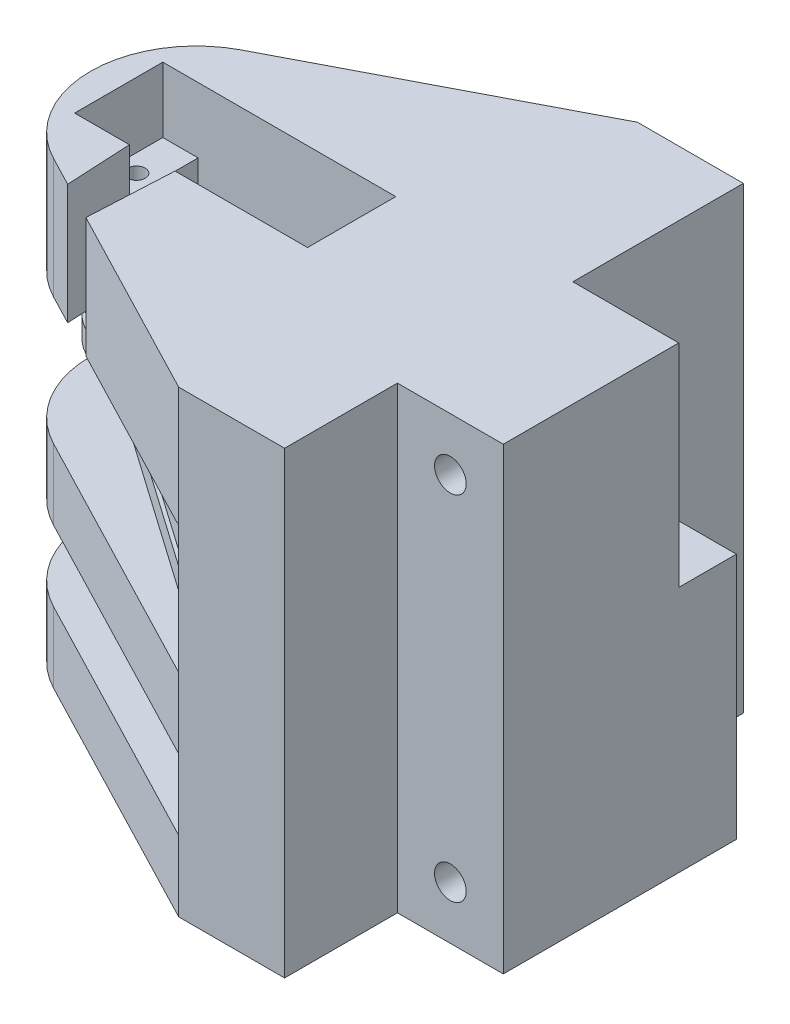
SolidWorks part; units mm, degrees
material "Copper"
ref_plane "Front Plane" through (0, 0, 0) normal (0, 0, 1) x (1, 0, 0)
ref_plane "Top Plane" through (0, 0, 0) normal (0, 1, 0) x (1, 0, 0)
ref_plane "Right Plane" through (0, 0, 0) normal (1, 0, 0) x (0, 0, -1)
sketch "Sketch1" plane through (0, 0, 0) normal (0, 0, 1) x (1, 0, 0)
  line L1 (0, 0) -> (75, 0)
  line L2 (0, 0) -> (0, 65)
  line L3 (0, 65) -> (75, 65)
  line L4 (75, 0) -> (75, 65)
  dimension "D1" = 65
  dimension "D2" = 75
extrude "Boss-Extrude1" add sketch "Sketch1" along normal blind 65
sketch "Sketch3" plane through (0, 0, 0) normal (0, -1, 0) x (1, 0, 0)
  line L0 (75, 32.5) -> (0, 32.5) construction
  line L1 (75, 65) -> (75, 0) construction
  line L2 (0, 65) -> (0, 0) construction
  line L3 (60, 49.01) -> (60, 32.5) construction
  line L4 (75, 65) -> (60, 65)
  line L5 (75, 65) -> (75, 49.01)
  line L6 (75, 49.01) -> (60, 49.01)
  line L7 (60, 65) -> (60, 49.01)
  line L8 (75, 0) -> (60, 0)
  line L9 (75, 0) -> (75, 15.99)
  line L10 (75, 15.99) -> (60, 15.99)
  line L11 (60, 0) -> (60, 15.99)
  line L12 (60, 32.5) -> (60, 15.99) construction
  dimension "D1" = 15
  dimension "D2" = 16.51
extrude "Cut-Extrude1" cut sketch "Sketch3" against normal blind 65.72
sketch "Sketch4" plane through (0, 0, 49.01) normal (0, 0, 1) x (1, 0, 0)
  line L0 (67.5, 0) -> (67.5, 65) construction
  line L1 (60, 0) -> (75, 0) construction
  line L2 (67.5, 7.5) -> (67.5, 0) construction
  line L3 (60, 65) -> (75, 65) construction
  line L4 (67.5, 65) -> (67.5, 57.5) construction
  circle A0 centre (67.5, 7.5) radius 2.2451
  circle A1 centre (67.5, 57.5) radius 2.2451
  dimension "D1" = 4.4901
  dimension "D3" = 7.5
  dimension "D4" = 4.4901
  dimension "D2" = 7.5
extrude "Cut-Extrude2" cut sketch "Sketch4" against normal blind 45.72
sketch "Sketch5" plane through (0, 0, 0) normal (-1, 0, 0) x (0, 0, 1)
  line L0 (65, 65) -> (65, 0) construction
  line L1 (0, 0) -> (65, 0)
  line L2 (0, 0) -> (0, 10)
  line L3 (0, 10) -> (65, 10)
  line L4 (65, 0) -> (65, 10)
  line L6 (0, 10) -> (65, 10)
  line L7 (0, 10) -> (0, 20)
  line L8 (0, 20) -> (65, 20)
  line L9 (65, 10) -> (65, 20)
  line L10 (0, 20) -> (65, 20)
  line L11 (0, 20) -> (0, 30)
  line L12 (0, 30) -> (65, 30)
  line L13 (65, 20) -> (65, 30)
  line L14 (0, 30) -> (65, 30)
  line L15 (0, 30) -> (0, 40)
  line L16 (0, 40) -> (65, 40)
  line L17 (65, 30) -> (65, 40)
  line L18 (0, 40) -> (65, 40)
  line L19 (0, 40) -> (0, 43)
  line L20 (0, 43) -> (65, 43)
  line L21 (65, 40) -> (65, 43)
  line L22 (0, 43) -> (65, 43)
  line L23 (0, 43) -> (0, 45)
  line L24 (0, 45) -> (65, 45)
  line L25 (65, 43) -> (65, 45)
  line M3 (0, 65) -> (0, 0)
  line M5 (65, 0) -> (65, 65)
  dimension "D1" = 10
  dimension "D2" = 3
  dimension "D3" = 2
extrude "Cut-Extrude3" cut sketch "Sketch5" against normal blind 45 contours L16 L12 M3 M5 | L8 L3 M3 M5 | L23 L24 L25 L22 region at (0, 15, 32.5) region at (0, 35, 32.5)
sketch "Sketch6" plane through (0, 0, 0) normal (0, -1, 0) x (1, 0, 0)
  line L0 (0, 32.5) -> (48.8784, 32.5) construction
  line L1 (0, 65) -> (0, 0) construction
  line L2 (60, 0) -> (45, 0)
  line L3 (0, 0) -> (60, 0) construction
  line L4 (45, 0) -> (8.0816, 19.1907)
  line L5 (8.0816, 45.8093) -> (45, 65)
  line L6 (0, 65) -> (60, 65) construction
  line L7 (45, 0) -> (45, 65) construction
  line L8 (60, 15.99) -> (60, 0) construction
  line L9 (45, 14.0738) -> (60, 14.0738) construction
  line L10 (45, 0) -> (0, 0)
  line L11 (0, 0) -> (0, 32.5)
  line L12 (0, 32.5) -> (0, 65)
  line L13 (0, 65) -> (45, 65)
  circle A0 centre (15, 32.5) radius 15
  line M6 (60, 65) -> (0, 65)
  line M7 (0, 65) -> (0, 0)
  line M8 (0, 0) -> (60, 0)
  dimension "D1" = 15
  dimension "D2" = 30
extrude "Cut-Extrude4" cut sketch "Sketch6" against normal blind 65 contours A0 L4 M7 M8 | A0 L5 M6 M7 region at (14.6593, 0, 8.2233) region at (14.6593, 0, 56.7767)
sketch "Sketch10" plane through (0, 0, 0) normal (0, -1, 0) x (1, 0, 0)
  line L0 (0, 32.5) -> (15, 32.5) construction
  arc A0 (8.0816, 45.8093) -> (8.0816, 19.1907) centre (15, 32.5) ccw construction
  circle A1 centre (15, 32.5) radius 1
  dimension "D1" = 15
  dimension "D2" = 2
extrude "Cut-Extrude6" cut sketch "Sketch10" against normal blind 42
sketch "Sketch12" plane through (0, 65, 0) normal (0, 1, 0) x (1, 0, 0)
  line L0 (0, -32.5) -> (43.2089, -32.5) construction
  line L2 (15, -32.5) -> (0, -32.5) construction
  line L3 (20.2526, -29.6) -> (21.4526, -29.6)
  line L4 (21.4526, -35.4) -> (20.2526, -35.4)
  circle A0 centre (15, -32.5) radius 6
  circle A1 centre (21.4526, -32.5) radius 2.9
  arc A2 (8.0816, -19.1907) -> (8.0816, -45.8093) centre (15, -32.5) ccw construction
  dimension "D1" = 12
  dimension "D3" = 5.8
  dimension "D2" = 15
  dimension "D4" = 1.2
extrude "Cut-Extrude7" cut sketch "Sketch12" against normal blind 20 contours A1 A0 | A1 A0 | A0 A1 | A1 L3 A0 | A1 A0 L4 | A0 region at (14.5616, 65, 32.5) region at (20.5934, 65, 29.6641) region at (22.3237, 65, 32.5) region at (20.5934, 65, 35.3359) region at (19.8631, 65, 32.5)
sketch "Sketch14" plane through (0, 65, 0) normal (0, 1, 0) x (1, 0, 0)
  line L0 (0, -32.5) -> (49.7472, -32.5) construction
  line L2 (32, -32.5) -> (49.7472, -32.5) construction
  line L3 (9, -26.25) -> (32, -26.25)
  line L4 (9, -26.25) -> (9, -38.75)
  line L5 (9, -38.75) -> (32, -38.75)
  line L6 (32, -26.25) -> (32, -38.75)
  line L7 (15, -26.5) -> (15, -38.5) construction
  line L8 (32, -32.5) -> (24.3526, -32.5) construction
  line L9 (15, -26.5) -> (15, -26.25) construction
  arc A0 (20.2526, -29.6) -> (20.2526, -35.4) centre (15, -32.5) ccw construction
  arc A1 (21.4526, -35.4) -> (21.4526, -29.6) centre (21.4526, -32.5) ccw construction
  arc A2 (8.0816, -19.1907) -> (8.0816, -45.8093) centre (15, -32.5) ccw construction
  dimension "D1" = 23
  dimension "D2" = 12.5
extrude "Cut-Extrude9" cut sketch "Sketch14" against normal blind 13.75
sketch "Sketch16" plane through (0, 65, 0) normal (0, 1, 0) x (1, 0, 0)
  line L0 (32, -26.25) -> (9, -26.25) construction
  line L1 (9, -38.75) -> (4, -38.75)
  line L2 (9, -38.75) -> (9, -26.25)
  line L3 (9, -26.25) -> (4, -26.25)
  line L4 (4, -38.75) -> (4, -26.25)
  line L5 (32, -26.25) -> (37, -26.25)
  line L6 (32, -26.25) -> (32, -38.75)
  line L7 (32, -38.75) -> (37, -38.75)
  line L8 (37, -26.25) -> (37, -38.75)
  line L9 (4, -32.5) -> (9, -32.5) construction
  line L10 (32, -32.5) -> (37, -32.5) construction
  circle A2 centre (6.5, -32.5) radius 1.25
  circle A3 centre (34.5, -32.5) radius 1.25
  line M8 (9, -38.75) -> (9, -26.25)
  line M10 (32, -26.25) -> (32, -38.75)
  dimension "D2" = 2.5
  dimension "D1" = 5
extrude "Cut-Extrude10" cut sketch "Sketch16" against normal blind 9.25 contours A2 | L4 L1 L3 A2 M8 | L8 L5 L7 A3 M10 | A3 region at (6.5, 65, 38.6154) region at (34.5, 65, 26.3846) region at (6.5, 65, 32.5) region at (34.5, 65, 32.5)
extrude "Cut-Extrude11" cut sketch "Sketch16<4>" against normal blind 12.5 contours A2 | A3 region at (6.5, 65, 32.5) region at (34.5, 65, 32.5)
sketch "Sketch16<4>" plane through (0, 65, 0) normal (0, 1, 0) x (1, 0, 0) same geometry as "Sketch16"
sketch "Sketch18" plane through (0, 65, 0) normal (0, 1, 0) x (1, 0, 0)
  line L0 (15, -32.5) -> (0, -32.5) construction
  line L1 (11.45, -29) -> (18.55, -29)
  line L2 (11.45, -29) -> (11.45, -52.0042)
  line L3 (11.45, -52.0042) -> (18.55, -52.0042)
  line L4 (18.55, -29) -> (18.55, -52.0042)
  line L5 (15, -29) -> (15, -32.5) construction
  line L6 (11.45, -32.5) -> (12.45, -52.0042)
  line L7 (18.55, -32.5) -> (17.55, -52.0042)
  line L8 (12.45, -52.0042) -> (11.45, -52.0042) construction
  line L9 (17.55, -52.0042) -> (18.55, -52.0042) construction
  arc A0 (8.0816, -19.1907) -> (8.0816, -45.8093) centre (15, -32.5) ccw construction
  circle A2 centre (15, -32.5) radius 3.55
  line M9 (37, -38.75) -> (4, -38.75)
  line M11 (8.0816, -45.8093) -> (45, -65)
  dimension "D1" = 3.5
  dimension "D2" = 7.1
  dimension "D3" = 1
extrude "Cut-Extrude12" cut sketch "Sketch18" against normal blind 21.5 contours A2 L6 L7 M9 | L7 A2 L1 L6 | L1 A2 | L7 L6 M9 M11 region at (15, 65, 28.98) region at (15, 65, 32.5035) region at (15, 65, 36.9512) region at (15.1066, 65, 43.9327)
sketch "Sketch19" plane through (0, 40, 0) normal (0, -1, 0) x (1, 0, 0)
  line L0 (45, 65) -> (15, 44)
  line L1 (45, 0) -> (15, 21)
  circle A2 centre (15, 32.5) radius 11.5
  line M2 (45, 65) -> (8.0816, 45.8093)
  arc M3 (8.0816, 45.8093) -> (8.0816, 19.1907) centre (15, 32.5) ccw
  line M4 (8.0816, 19.1907) -> (45, 0)
  dimension "D1" = 23
extrude "Cut-Extrude13" cut sketch "Sketch19" against normal blind 8 contours A2 L0 L1 M2 M3 M4 region at (29.5466, 40, 55.1477)
sketch "Sketch20" plane through (0, 30, 0) normal (0, 1, 0) x (1, 0, 0)
  circle A0 centre (15, -32.5) radius 2
  dimension "D1" = 4
extrude "Boss-Extrude2" add sketch "Sketch20" along normal blind 0.5
sketch "Sketch21" plane through (0, 10, 0) normal (0, 1, 0) x (1, 0, 0)
  circle A0 centre (15, -32.5) radius 2
extrude "Boss-Extrude3" add sketch "Sketch21" along normal blind 0.5
sketch "Sketch22" plane through (0, 0, 0) normal (0, -1, 0) x (1, 0, 0)
  circle A0 centre (15, 32.5) radius 1
extrude "Cut-Extrude14" cut sketch "Sketch22" against normal blind 30.5
sketch "Sketch23" plane through (0, 65, 0) normal (0, 1, 0) x (1, 0, 0)
  line L0 (75, -49.01) -> (75, -15.99) construction
  line L1 (60, -15.99) -> (75, -15.99)
  line L2 (60, -15.99) -> (60, -24.1528)
  line L3 (60, -24.1528) -> (75, -24.1528)
  line L4 (75, -15.99) -> (75, -24.1528)
extrude "Cut-Extrude15" cut sketch "Sketch23" against normal blind 30
